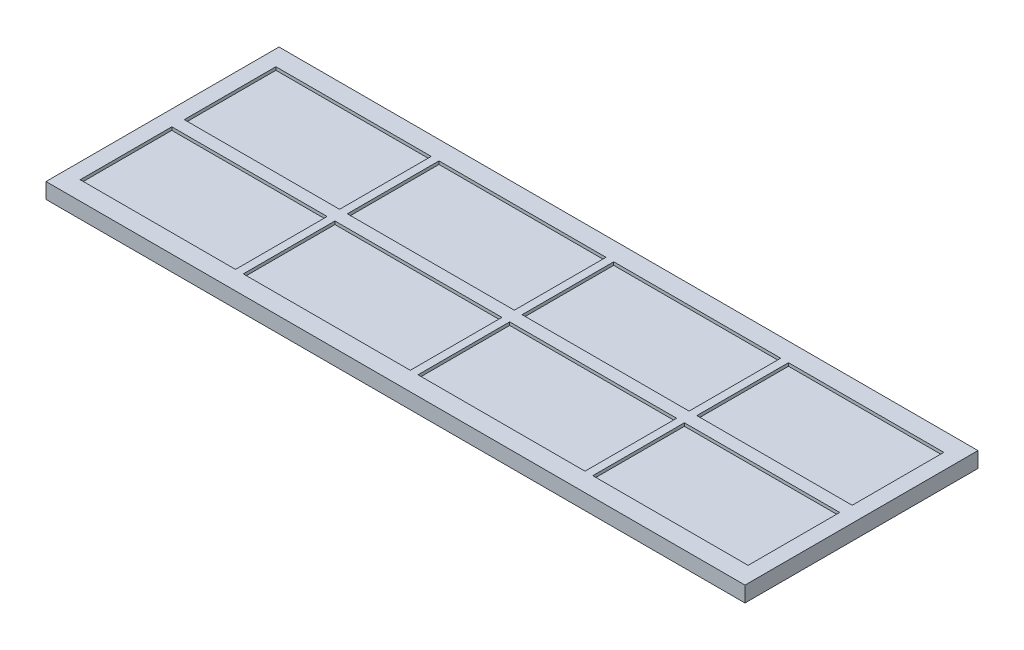
SolidWorks part; units mm, degrees
ref_plane "Front Plane" through (0, 0, 0) normal (0, 0, 1) x (1, 0, 0)
ref_plane "Top Plane" through (0, 0, 0) normal (0, 1, 0) x (1, 0, 0)
ref_plane "Right Plane" through (0, 0, 0) normal (1, 0, 0) x (0, 0, -1)
sketch "Sketch1" plane through (0, 0, 0) normal (0, 1, 0) x (1, 0, 0)
  line L0 (0, 2831.2577) -> (0, -2580.4974) construction
  line L1 (-225, 75) -> (225, 75)
  line L2 (-225, 75) -> (-225, -75)
  line L3 (-225, -75) -> (225, -75)
  line L4 (225, 75) -> (225, -75)
  line L5 (-225, 75) -> (225, -75) construction
  line L6 (-225, -75) -> (225, 75) construction
  line L7 (-225, 4) -> (225, 4)
  line L8 (-225, 4) -> (-225, -4)
  line L9 (-225, -4) -> (225, -4)
  line L10 (225, 4) -> (225, -4)
  line L11 (-225, 4) -> (225, -4) construction
  line L12 (-225, -4) -> (225, 4) construction
  line L13 (-2.5, 75) -> (2.5, 75)
  line L14 (-2.5, 75) -> (-2.5, -75)
  line L15 (-2.5, -75) -> (2.5, -75)
  line L16 (2.5, 75) -> (2.5, -75)
  line L17 (-2.5, 75) -> (2.5, -75) construction
  line L18 (-2.5, -75) -> (2.5, 75) construction
  line L19 (-112.5, 3396.926) -> (-112.5, -3321.1148) construction
  line L20 (115, 75) -> (115, -75)
  line L21 (-115, 75) -> (-110, 75)
  line L22 (-115, 75) -> (-115, -75)
  line L23 (-115, -75) -> (-110, -75)
  line L24 (-110, 75) -> (-110, -75)
  line L25 (-115, 75) -> (-110, -75) construction
  line L26 (-115, -75) -> (-110, 75) construction
  line L27 (110, 75) -> (110, -75)
  line L28 (110, 75) -> (115, 75)
  line L29 (110, -75) -> (115, -75)
  line L31 (-215, 63) -> (215, 63)
  line L32 (-215, 63) -> (-215, -63)
  line L33 (-215, -63) -> (215, -63)
  line L34 (215, 63) -> (215, -63)
  line L35 (-215, 63) -> (215, -63) construction
  line L36 (-215, -63) -> (215, 63) construction
  point P0 (0, 0)
  point P6 (0, 0)
  point P11 (0, 0)
  point P20 (-112.5, 0)
  point P25 (0, 0)
  dimension "D1" = 450
  dimension "D2" = 150
  dimension "D3" = 8
  dimension "D4" = 5
  dimension "D5" = 112.5
  dimension "D6" = 5
  dimension "D7" = 12
  dimension "D8" = 10
extrude "Boss-Extrude1" add sketch "Sketch1" along normal blind 8 contours L31 L32 L7 L22 | L32 L33 L22 L9 | L24 L33 L14 L9 | L31 L24 L7 L14 | L31 L16 L7 L27 | L16 L33 L27 L9 | L34 L31 L20 L7 | L34 L9 L20 L33 region at (-165, 0, -33.5) region at (-56.25, 0, -33.5) region at (-165, 0, 33.5) region at (56.25, 0, -33.5) region at (-56.25, 0, 33.5) region at (165, 0, -33.5) region at (56.25, 0, 33.5) region at (165, 0, 33.5)
extrude "Boss-Extrude2" add sketch "Sketch1<3>" along normal blind 10 contours L32 L31 L22 L1 L2 L7 | L33 L32 L9 L2 L3 L22 | L33 L24 L3 L14 | L33 L16 L3 L27 | L9 L34 L33 L20 L3 L4 | L24 L31 L14 L1 | L16 L31 L27 L1 | L31 L34 L7 L4 L1 L20 | L32 L7 L2 L9 | L7 L32 L9 L22 | L22 L23 L24 L21 | L16 L15 L14 L13 | L7 L10 L9 L8 | L20 L29 L27 L28 region at (-170, 0, -73.6908) region at (-220, 0, 0) region at (-56.25, 0, -69) region at (-220, 0, 5.3092) region at (-165, 0, 0) region at (56.25, 0, -69) region at (-56.25, 0, 69) region at (170, 0, -73.6908) region at (56.25, 0, 69) region at (223.6908, 0, 39.5)
sketch "Sketch1<3>" plane through (0, 0, 0) normal (0, 1, 0) x (1, 0, 0) same geometry as "Sketch1"
